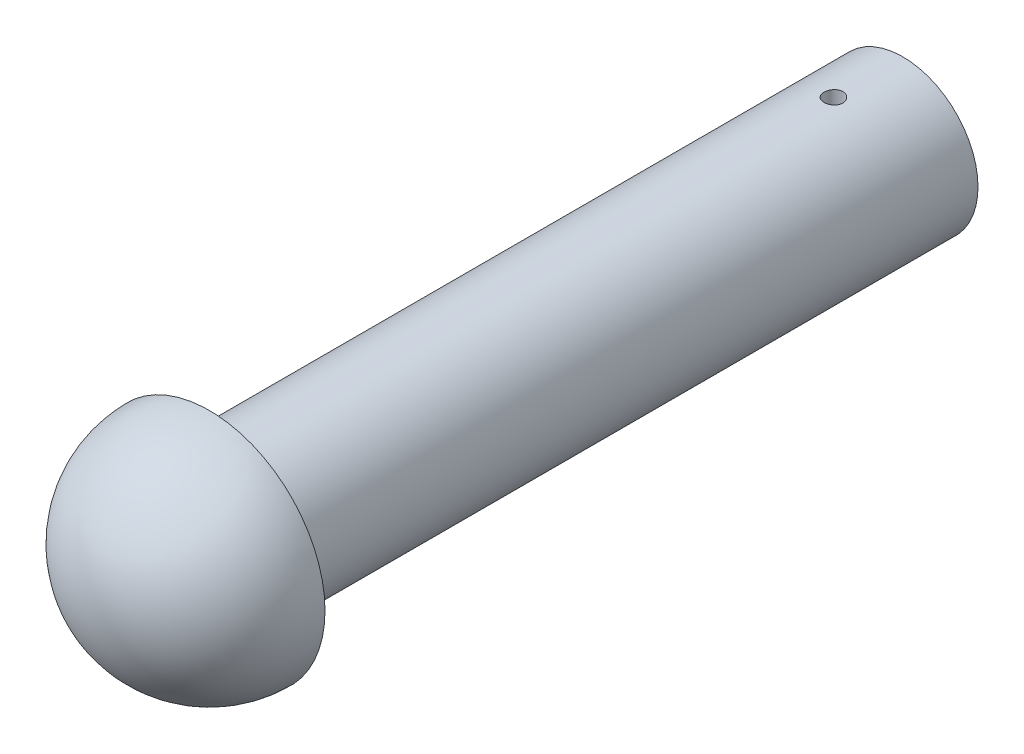
SolidWorks part; units mm, degrees
ref_plane "Front Plane" through (0, 0, 0) normal (0, 0, 1) x (1, 0, 0)
ref_plane "Top Plane" through (0, 0, 0) normal (0, 1, 0) x (1, 0, 0)
ref_plane "Right Plane" through (0, 0, 0) normal (1, 0, 0) x (0, 0, -1)
sketch "Sketch1" plane through (0, 0, 0) normal (0, 0, 1) x (1, 0, 0)
  circle A0 centre (0, 0) radius 9.75
  dimension "D1" = 19.5
extrude "Boss-Extrude1" add sketch "Sketch1" along normal blind 90
sketch "Sketch2" plane through (0, 0, 90) normal (0, 0, 1) x (1, 0, 0)
  line L0 (0, 15) -> (0, -15)
  arc A0 (0, -15) -> (0, 15) centre (0, 0) ccw
  dimension "D1" = 15
revolve "Revolve1" add sketch "Sketch2" angle 180 about L0
sketch "Sketch3" plane through (0, 0, 0) normal (0, 1, 0) x (1, 0, 0)
  circle A0 centre (0.0082, -9.0234) radius 1.2212
extrude "Cut-Extrude1" cut sketch "Sketch3" against normal blind 22 and the other way blind 22
